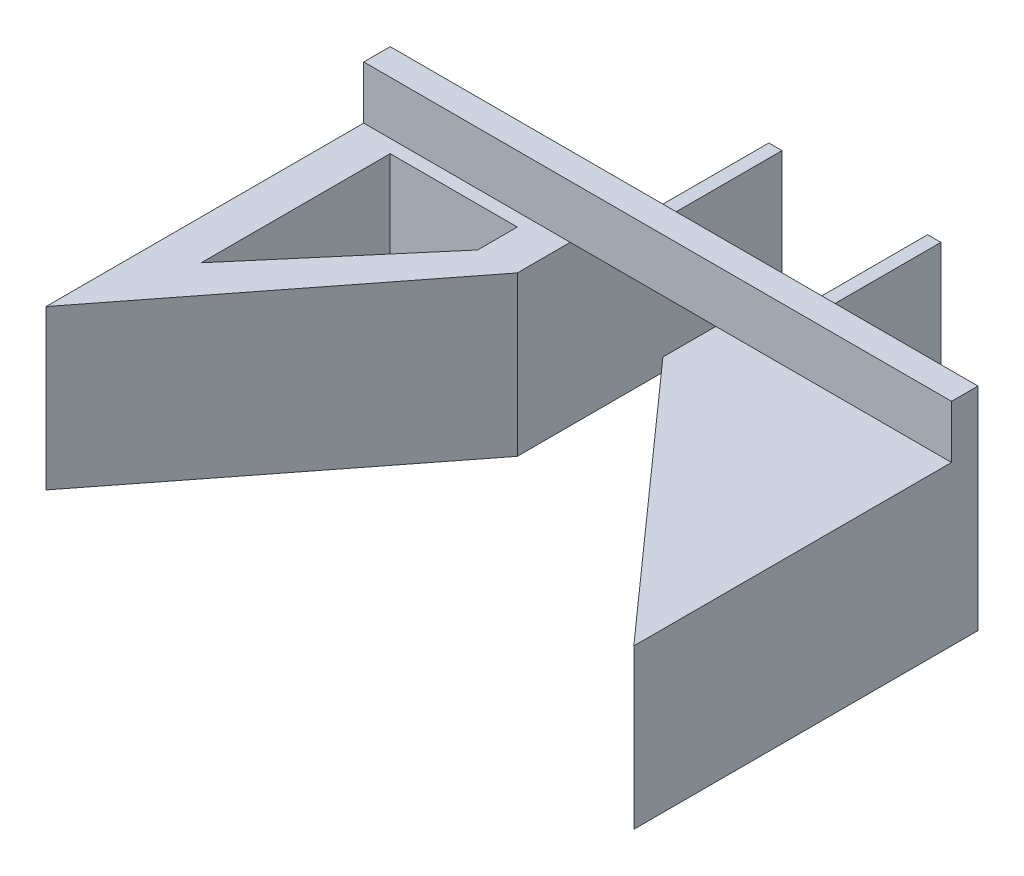
SolidWorks part; units mm, degrees
ref_plane "Front Plane" through (0, 0, 0) normal (0, 0, 1) x (1, 0, 0)
ref_plane "Top Plane" through (0, 0, 0) normal (0, 1, 0) x (1, 0, 0)
ref_plane "Right Plane" through (0, 0, 0) normal (1, 0, 0) x (0, 0, -1)
sketch "Sketch1" plane through (0, 0, 0) normal (0, 1, 0) x (1, 0, 0)
  line L0 (0, 42.7008) -> (0, 27.7008)
  line L1 (0, 42.7008) -> (89, 42.7008)
  line L2 (0, 0) -> (-49.1968, 0) construction
  line L3 (-49.1968, 0) -> (52.6104, 0) construction
  line L4 (-133, 12.7008) -> (-133, -87.2992)
  line L5 (-133, -87.2992) -> (-55, 12.7008)
  line L13 (-133, 42.7008) -> (-55, 42.7008)
  line L14 (-55, 12.7008) -> (-55, 42.7008)
  line L20 (-133, 42.7008) -> (-133, 12.7008)
  line L26 (-118, 27.7008) -> (-118, -43.6794)
  line L27 (-118, -43.6794) -> (-70, 12.7008)
  line L28 (-70, 12.7008) -> (-70, 27.7008)
  line L29 (-70, 27.7008) -> (-118, 27.7008)
  line L39 (89, 42.7008) -> (89, -87.2992)
  line L40 (89, -87.2992) -> (0, 12.7008)
  line L41 (0, 12.7008) -> (0, 27.7008)
  dimension "D1" = 55
  dimension "D2" = 78
  dimension "D3" = 100
  dimension "D4" = 30
  dimension "D5" = 15
  dimension "D6" = 15
  dimension "D7" = 15
  dimension "D8" = 15
  dimension "D9" = 89
extrude "Boss-Extrude1" add sketch "Sketch1" along normal blind 60
sketch "Sketch3" plane through (0, 60, 0) normal (0, 1, 0) x (1, 0, 0)
  line L13 (-133, 42.7008) -> (-133, -87.2992) construction
  line L14 (89, 42.7008) -> (-133, 42.7008)
  line L15 (89, 42.7008) -> (89, 32.7008)
  line L16 (89, 32.7008) -> (-133, 32.7008)
  line L17 (-133, 42.7008) -> (-133, 32.7008)
  dimension "D1" = 10
extrude "Boss-Extrude3" add sketch "Sketch3" along normal blind 20
ref_plane "Plane1" through (0, 0, 0) normal (0, -1, 0) x (-1, 0, 0)
sketch "Sketch4" plane through (0, 0, 0) normal (0, -1, 0) x (-1, 0, 0)
  line L1 (55, 42.7008) -> (60, 42.7008)
  line L2 (55, 42.7008) -> (55, 112.7008)
  line L3 (55, 112.7008) -> (60, 112.7008)
  line L4 (60, 42.7008) -> (60, 112.7008)
  dimension "D1" = 70
  dimension "D2" = 5
extrude "Boss-Extrude4" add sketch "Sketch4" against normal blind 50
sketch "Sketch5" plane through (0, 0, 0) normal (0, -1, 0) x (-1, 0, 0)
  line L0 (-89, 42.7008) -> (133, 42.7008) construction
  line L1 (0, 42.7008) -> (-5, 42.7008)
  line L2 (0, 42.7008) -> (0, 112.7008)
  line L3 (0, 112.7008) -> (-5, 112.7008)
  line L4 (-5, 42.7008) -> (-5, 112.7008)
  line L6 (0, 42.7008) -> (0, 12.7008) construction
  point P6 (0, 0)
  dimension "D1" = 5
  dimension "D2" = 70
  dimension "D3" = 0
extrude "Boss-Extrude5" add sketch "Sketch5" against normal blind 50
